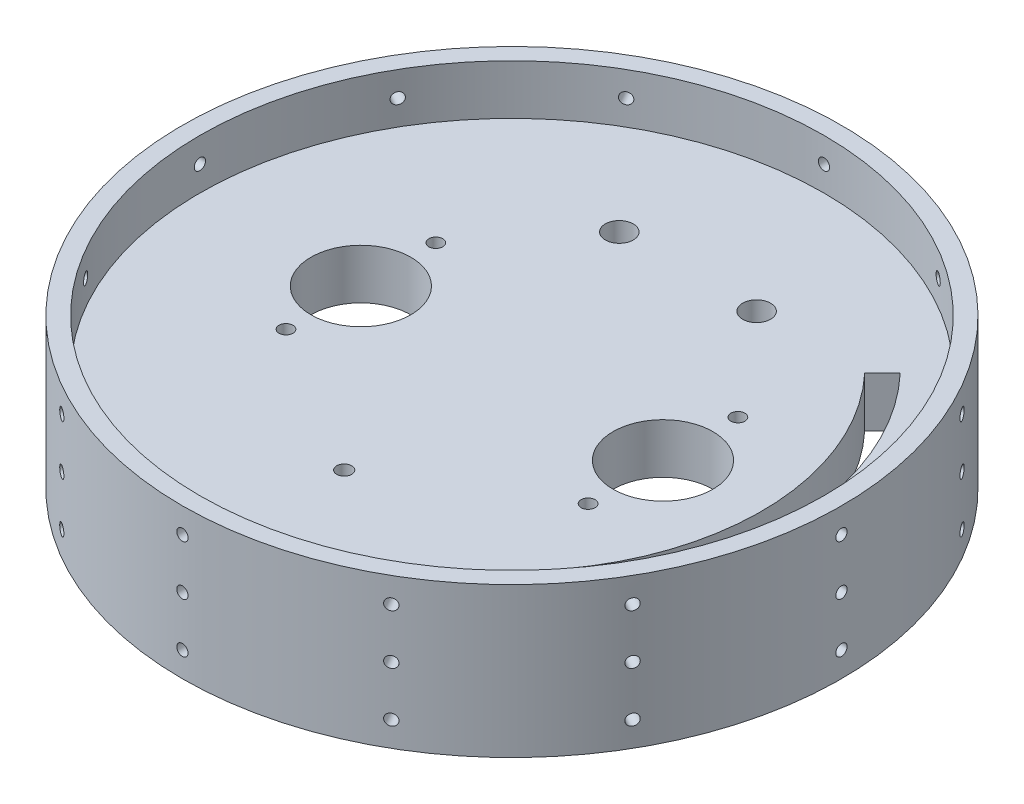
SolidWorks part; units mm, degrees
material "6061-T6 (SS)"
ref_plane "Front" through (0, 0, 0) normal (0, 0, 1) x (1, 0, 0)
ref_plane "Top" through (0, 0, 0) normal (0, 1, 0) x (1, 0, 0)
ref_plane "Right" through (0, 0, 0) normal (1, 0, 0) x (0, 0, -1)
sketch "Sketch1" plane through (0, 0, 0) normal (0, 1, 0) x (1, 0, 0)
  line L1 (0, 0) -> (127.635, 0)
  line L2 (0, 0) -> (0, 127.635)
  line L3 (0, 127.635) -> (127.635, 127.635)
  line L4 (127.635, 0) -> (127.635, 127.635)
  dimension "D1" = 127.635
  dimension "D2" = 127.635
extrude "Main Plate" add sketch "Sketch1" along normal blind 12.7
sketch "Sketch9" plane through (0, 12.7, 0) normal (0, 1, 0) x (1, 0, 0)
  circle A0 centre (63.8175, 63.8175) radius 85.725
  dimension "D1" = 171.45
extrude "Boss-Extrude1" add sketch "Sketch9" against normal up to surface (12.7 mm away) contours A0 up to face at (63.8175, 0, -63.8175)
sketch "Sketch10" plane through (0, 12.7, 0) normal (0, 1, 0) x (1, 0, 0)
  circle A0 centre (63.8175, 63.8175) radius 97.0396
  circle A1 centre (63.8175, 63.8175) radius 83.82
extrude "Cut-Extrude1" cut sketch "Sketch10" against normal blind 167.64 contours A0 | A1
sketch "Sketch11" plane through (0, 12.7, 0) normal (0, 1, 0) x (1, 0, 0)
  circle A0 centre (63.8175, 63.8175) radius 38.4175 construction
  circle A1 centre (63.8175, 63.8175) radius 42.8813 construction
  circle A2 centre (63.8175, 63.8175) radius 48.0528 construction
  circle A3 centre (63.8175, 63.8175) radius 83.82 construction
  dimension "D1" = 76.835
  dimension "D2" = 85.7626
  dimension "D3" = 96.1055
sketch "Sketch12" plane through (0, 12.7, 0) normal (0, 1, 0) x (1, 0, 0)
  line L0 (63.8175, 156.3529) -> (63.8175, -30.2474) construction
  line L1 (160.3603, 63.0527) -> (-31.9911, 63.0527) construction
  point P6 (63.8175, 63.0527)
sketch "Sketch2" plane through (0, 12.7, 0) normal (0, 1, 0) x (1, 0, 0)
  circle A0 centre (46.355, 108.585) radius 3.556
  circle A3 centre (63.8175, 63.8175) radius 48.0528 construction
  dimension "D1" = 7.112
extrude "U-Bolt Hole" cut sketch "Sketch2" against normal blind 12.7
pattern_linear "U-Bolt Pattern" count 2 spacing 34.925 along (1, 0, 0) of "U-Bolt Hole"
sketch "Sketch3" plane through (0, 12.7, 0) normal (0, 1, 0) x (1, 0, 0)
  circle A0 centre (25.4, 44.7675) radius 1.778
  circle A1 centre (63.8175, 63.8175) radius 42.8813 construction
  dimension "D1" = 3.556
extrude "Raptor Bolt Hole" cut sketch "Sketch3" against normal blind 12.7
pattern_linear "Raptor Bolt Pattern" count 2 spacing 38.1 along (0, 0, -1) count 2 spacing 76.835 along (1, 0, 0) of "Raptor Bolt Hole"
sketch "Sketch4" plane through (0, 12.7, 0) normal (0, 1, 0) x (1, 0, 0)
  circle A0 centre (25.4, 63.8175) radius 12.7
  circle A1 centre (63.8175, 63.8175) radius 38.4175 construction
  dimension "D1" = 25.4
extrude "Co2 Cylinder Hole" cut sketch "Sketch4" against normal blind 12.7
pattern_linear "Co2 Pattern" count 2 spacing 76.835 along (1, 0, 0) of "Co2 Cylinder Hole"
sketch "Sketch13" plane through (0, 12.7, 0) normal (0, 1, 0) x (1, 0, 0)
  line L0 (63.8175, 156.3529) -> (63.8175, -30.2474) construction
  circle A0 centre (63.8175, 21.1558) radius 1.905
  dimension "D1" = 3.81
extrude "Cut-Extrude2" cut sketch "Sketch13" against normal up to surface (12.7 mm away) up to face at (102.235, 0, -51.1175)
sketch "Sketch14" plane through (0, 12.7, 0) normal (0, 1, 0) x (1, 0, 0)
  line L0 (201.1692, 63.8175) -> (-73.4523, 63.8175) construction
ref_plane "Plane1" through (0, 0, -63.8175) normal (0, 0, -1) x (-1, 0, 0)
ref_plane "Plane3" through (0, 6.35, 0) normal (0, 1, 0) x (1, 0, 0)
sketch "Sketch16" plane through (0, 12.7, 0) normal (0, 1, 0) x (1, 0, 0)
  line L0 (63.8175, 63.8175) -> (123.0872, 123.0872) construction
  line L1 (63.8175, 63.8175) -> (123.0872, 4.5478) construction
  line L2 (92.202, 63.8175) -> (-92.202, 63.8175) construction
  line L3 (107.3987, 20.2363) -> (111.8888, 15.7462)
  line L4 (108.6773, 108.6773) -> (113.1913, 113.1913)
  circle A0 centre (63.8175, 63.8175) radius 83.82 construction
  arc A1 (113.1913, 113.1913) -> (111.8888, 15.7462) centre (62.4974, 65.1376) cw
  arc A2 (108.6773, 108.6773) -> (107.3987, 20.2363) centre (62.4754, 65.1156) cw
  dimension "D3" = 69.85
  dimension "D4" = 63.5
  dimension "D1" = 45
  dimension "D2" = 90
  dimension "D5" = 6.35
  dimension "D6" = 6.3837
extrude "Cut-Extrude4" cut sketch "Sketch16" against normal blind 15.24
ref_plane "Plane2" through (-20.0025, 0, 0) normal (-1, 0, 0) x (0, 0, 1)
sketch "Sketch18" plane through (0, 6.35, 0) normal (0, 1, 0) x (1, 0, 0)
  circle A0 centre (63.8175, 63.8175) radius 83.82
  circle A1 centre (63.8175, 63.8175) radius 79.375
  dimension "D1" = 158.75
extrude "Boss-Extrude2" add sketch "Sketch18" along normal mid plane 38.1
sketch "Sketch15" plane through (-20.0025, 0, 0) normal (-1, 0, 0) x (0, 0, 1)
  line L0 (-63.8175, 92.202) -> (-63.8175, -92.202) construction
  line L1 (20.0025, 12.7) -> (-147.6375, 12.7) construction
  line L2 (-147.6375, -12.7) -> (20.0025, -12.7) construction
  line L3 (15.5575, 25.4) -> (-143.1925, 25.4) construction
  circle A0 centre (-63.8175, 6.35) radius 1.4351
  circle A1 centre (-63.8175, 19.05) radius 1.4351
  circle A2 centre (-63.8175, -6.35) radius 1.4351
  dimension "D1" = 2.8702
  dimension "D2" = 6.35
  dimension "D3" = 2.8702
  dimension "D4" = 2.8702
  dimension "D5" = 6.35
  dimension "D6" = 6.35
extrude "Cut-Extrude3" cut sketch "Sketch15" against normal blind 15.24
pattern_circular "CirPattern1" count 12 over 360 about axis through (63.8175, -154.94, -63.8175) along (0, 1, 0) of "Cut-Extrude3" reverse direction yes
